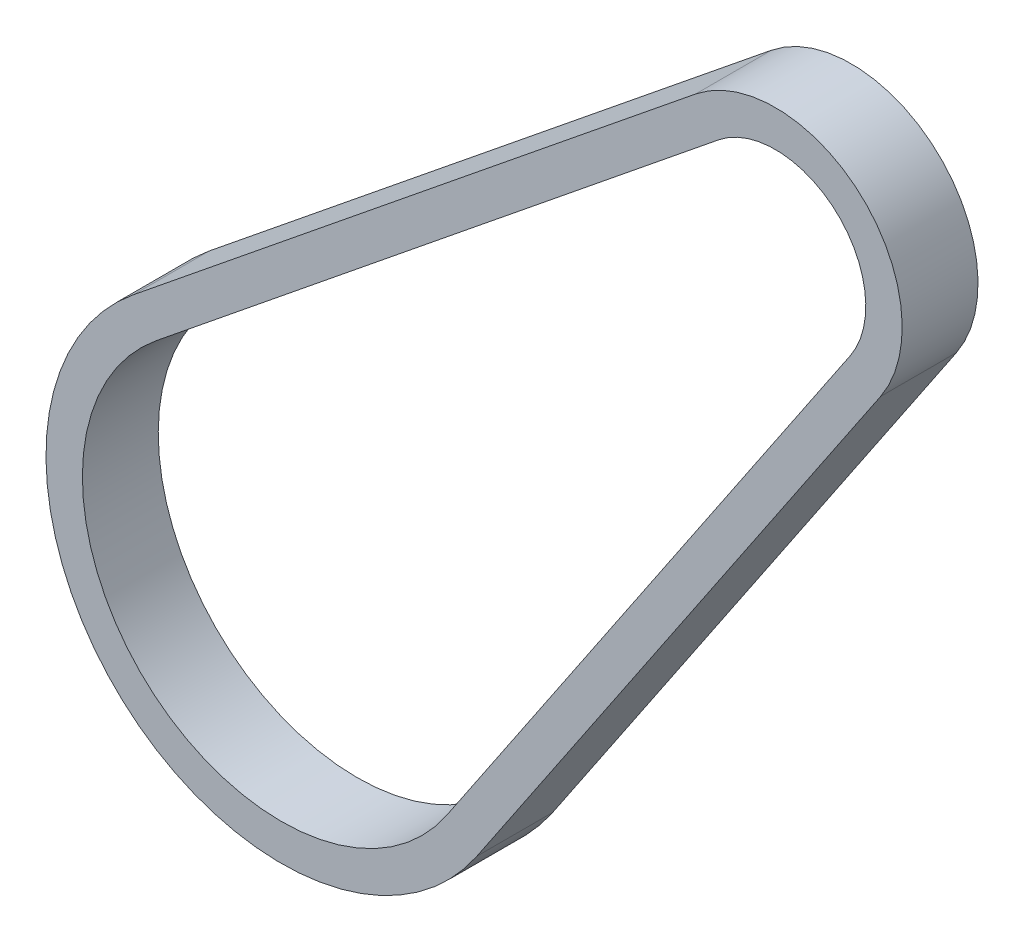
SolidWorks part; units mm, degrees
material "Rubber"
ref_plane "Front Plane" through (0, 0, 0) normal (0, 0, 1) x (1, 0, 0)
ref_plane "Top Plane" through (0, 0, 0) normal (0, 1, 0) x (1, 0, 0)
ref_plane "Right Plane" through (0, 0, 0) normal (1, 0, 0) x (0, 0, -1)
sketch "Sketch2" plane through (0, 0, 0) normal (0, 0, 1) x (1, 0, 0)
  line L0 (0, 0) -> (1, 0) construction
  line L1 (0, 0) -> (0, 1) construction
  line L2 (38.5026, 31.5645) -> (11.8842, -7.9963)
  line L3 (-9.0107, 11.1347) -> (28.0552, 41.13)
  arc A0 (28.0552, 41.13) -> (38.5026, 31.5645) centre (32.5605, 35.5626) cw
  arc A1 (11.8842, -7.9963) -> (-9.0107, 11.1347) centre (0, 0) cw
extrude "Extrude-Thin1" add sketch "Sketch2" against normal blind 5 thin thin type two direction wall 1.2 second wall 1.2
